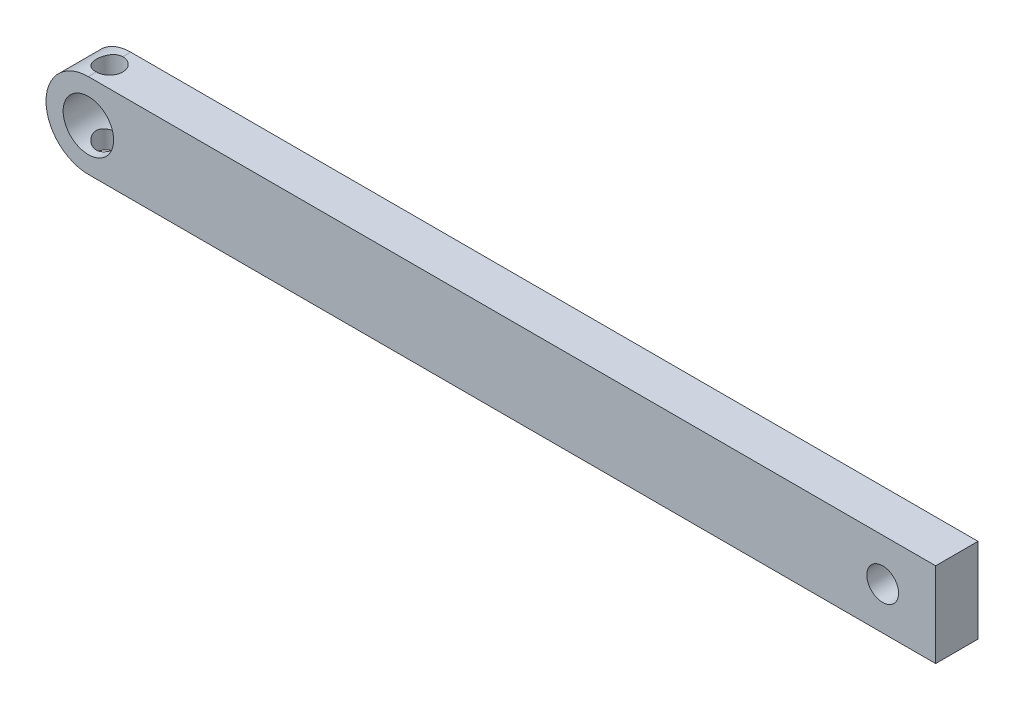
SolidWorks part; units mm, degrees
material "Plain Carbon Steel"
ref_plane "Front Plane" through (0, 0, 0) normal (0, 0, 1) x (1, 0, 0)
ref_plane "Top Plane" through (0, 0, 0) normal (0, 1, 0) x (1, 0, 0)
ref_plane "Right Plane" through (0, 0, 0) normal (1, 0, 0) x (0, 0, -1)
sketch "Sketch1" plane through (0, 0, 0) normal (0, 0, 1) x (1, 0, 0)
  line L0 (0, -8) -> (160, -8)
  line L1 (160, -8) -> (160, 8)
  line L2 (160, 8) -> (0, 8)
  arc A0 (0, 8) -> (0, -8) centre (0, 0) ccw
  dimension "D2" = 8
  dimension "D1" = 160
extrude "Boss-Extrude1" add sketch "Sketch1" along normal blind 8
sketch "Sketch2" plane through (0, 0, 0) normal (0, 0, 1) x (1, 0, 0)
  circle A0 centre (0, 0) radius 4.7625
  circle A1 centre (150, 0) radius 3
  dimension "D1" = 9.525
  dimension "D3" = 6
  dimension "D2" = 150
extrude "Cut-Extrude1" cut sketch "Sketch2" against normal mid plane 40
sketch "Sketch3" plane through (0, 0, 0) normal (0, 0, 1) x (1, 0, 0)
  circle A0 centre (30, 0) radius 4
  dimension "D2" = 8
  dimension "D1" = 30
extrude "Cut-Extrude2" cut sketch "Sketch3" against normal mid plane 1
sketch "Sketch4" plane through (0, 0, 0) normal (0, 1, 0) x (1, 0, 0)
  line L0 (0, -8) -> (0, 0) construction
  circle A0 centre (0, -4) radius 2.5
  dimension "D2" = 5
  dimension "D1" = 4
extrude "Cut-Extrude3" cut sketch "Sketch4" against normal mid plane 40
ref_axis "Axis1" through (0, 0, -0.4) along (0, 0, 1)
